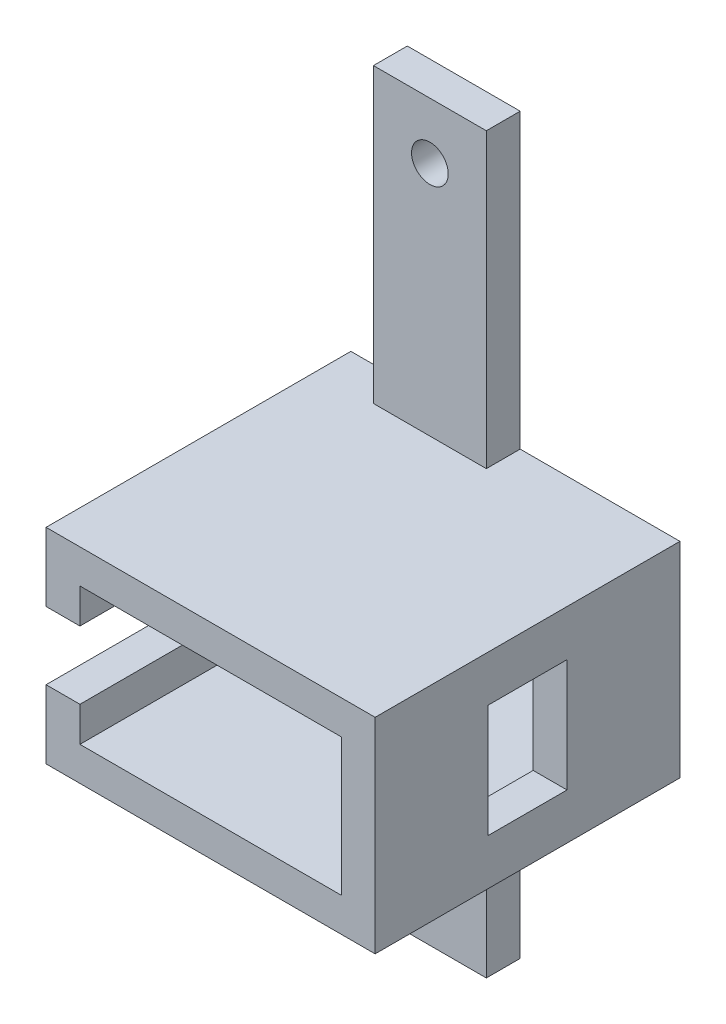
SolidWorks part; units mm, degrees
ref_plane "Plan de face" through (0, 0, 0) normal (0, 0, 1) x (1, 0, 0)
ref_plane "Plan de dessus" through (0, 0, 0) normal (0, 1, 0) x (1, 0, 0)
ref_plane "Plan de droite" through (0, 0, 0) normal (1, 0, 0) x (0, 0, -1)
sketch "Esquisse1" plane through (0, 0, 0) normal (0, 0, 1) x (1, 0, 0)
  line L0 (10, -44.075) -> (10, -65)
  line L1 (0, 0) -> (10, 0)
  line L2 (0, 0) -> (0, -25.925)
  line L3 (0, -65) -> (10, -65)
  line L9 (21.15, -28.925) -> (-2, -28.925)
  line L10 (21.15, -28.925) -> (21.15, -41.075)
  line L11 (21.15, -41.075) -> (-2, -41.075)
  line L12 (-2, -28.925) -> (-2, -41.075)
  line L13 (10, 0) -> (10, -25.925)
  line L14 (0, -44.075) -> (0, -65)
  line L15 (24.15, -25.925) -> (10, -25.925)
  line L16 (24.15, -25.925) -> (24.15, -44.075)
  line L17 (24.15, -44.075) -> (10, -44.075)
  line L18 (-5, -25.925) -> (-5, -44.075)
  line L19 (0, -25.925) -> (-5, -25.925)
  line L20 (0, -44.075) -> (-5, -44.075)
  line L21 (0, -25.925) -> (10, -25.925)
  line L22 (10, -44.075) -> (0, -44.075)
  point P15 (-2, -35)
  point P16 (5, -65)
  dimension "D1" = 10
  dimension "D2" = 65
  dimension "D3" = 3
  dimension "D4" = 3
  dimension "D5" = 23.15
  dimension "D6" = 12.15
  dimension "D7" = 30
  dimension "D8" = 7
  dimension "D9" = 3
  dimension "D10" = 3
extrude "Boss.-Extru.1" add sketch "Esquisse1" along normal blind 3 contours L2 L21 L13 L1 | L0 L22 L14 L3 region at (5, -54.5375, 0) region at (5, -12.9625, 0)
extrude "Boss.-Extru.2" add sketch "Esquisse1<3>" along normal blind 27 contours L22 L17 L16 L15 L21 L19 L18 L20 L12 L9 L10 L11 region at (5, -43.7316, 0)
sketch "Esquisse1<3>" plane through (0, 0, 0) normal (0, 0, 1) x (1, 0, 0) same geometry as "Esquisse1"
sketch "Esquisse3" plane through (0, 0, 3) normal (0, 0, 1) x (1, 0, 0)
  line L0 (0, 0) -> (10, 0) construction
  circle A0 centre (5, -5) radius 1.625
  point P5 (5, 0)
  dimension "D1" = 3.25
  dimension "D2" = 5
extrude "Enlèv. mat.-Extru.2" cut sketch "Esquisse3" against normal through all contours A0
pattern_linear "Répétition linéaire1" count 2 spacing 55 along (0, -1, 0) of "Enlèv. mat.-Extru.2"
sketch "Esquisse5" plane through (-5, 0, 0) normal (-1, 0, 0) x (0, 0, 1)
  line L0 (0, -25.925) -> (0, -44.075) construction
  line L1 (0, -32) -> (27, -32)
  line L2 (0, -32) -> (0, -38)
  line L3 (0, -38) -> (27, -38)
  line L4 (27, -32) -> (27, -38)
  line L5 (27, -25.925) -> (27, -44.075) construction
  point P8 (0, -35)
  point P9 (0, -35)
  dimension "D1" = 6
extrude "Enlèv. mat.-Extru.3" cut sketch "Esquisse5" against normal blind 10
sketch "Esquisse6" plane through (24.15, 0, 0) normal (1, 0, 0) x (0, 0, -1)
  line L0 (-27, -25.925) -> (0, -25.925) construction
  line L1 (-17, -30) -> (-10, -30)
  line L2 (-17, -30) -> (-17, -40)
  line L3 (-17, -40) -> (-10, -40)
  line L4 (-10, -30) -> (-10, -40)
  line L5 (-27, -25.925) -> (-27, -44.075) construction
  point P6 (-13.5, -25.925)
  point P7 (-13.5, -30)
  point P10 (-27, -35)
  point P11 (-17, -35)
  dimension "D1" = 10
  dimension "D2" = 7
extrude "Enlèv. mat.-Extru.4" cut sketch "Esquisse6" against normal up to next
